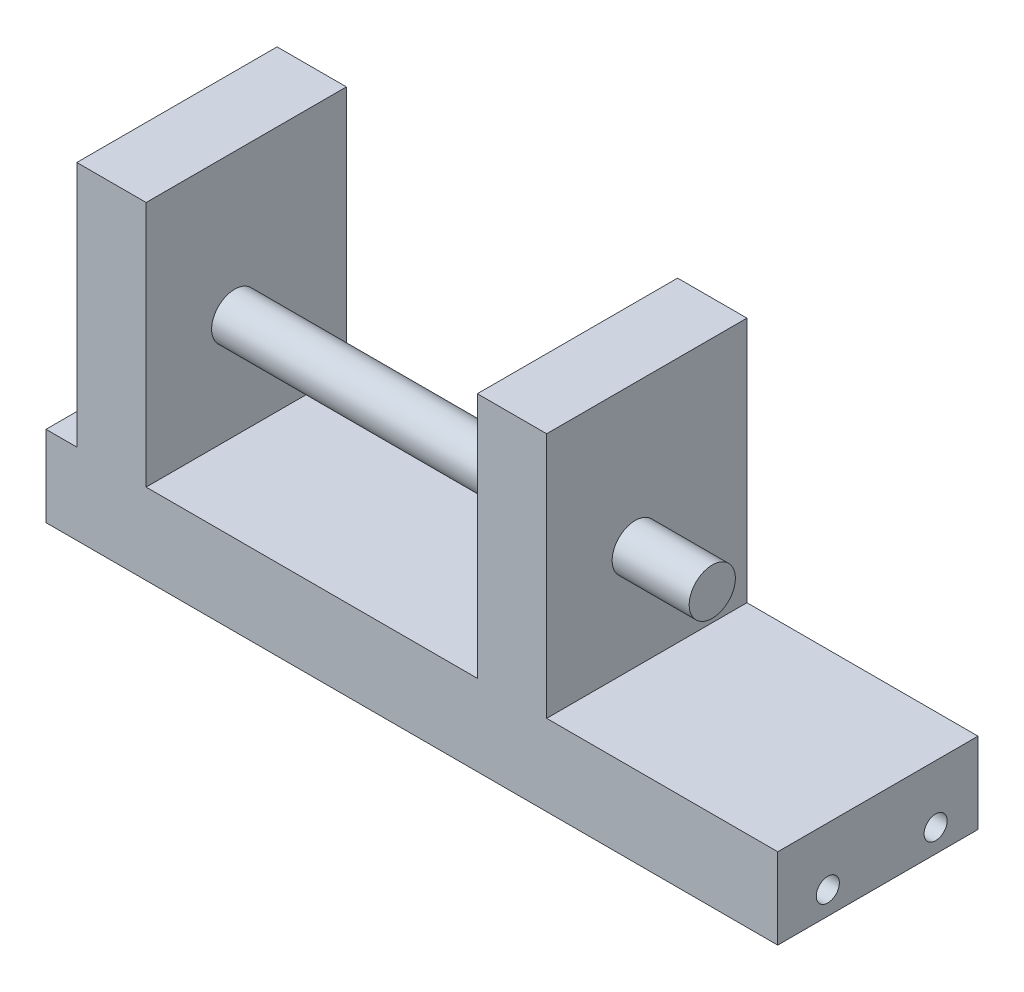
SolidWorks part; units mm, degrees
ref_plane "前视基准面" through (0, 0, 0) normal (0, 0, 1) x (1, 0, 0)
ref_plane "上视基准面" through (0, 0, 0) normal (0, 1, 0) x (1, 0, 0)
ref_plane "右视基准面" through (0, 0, 0) normal (1, 0, 0) x (0, 0, -1)
sketch "草图1" plane through (0, 0, 0) normal (1, 0, 0) x (0, 0, -1)
  line L0 (-19.5, 10.5) -> (-19.5, 3) construction
  line L1 (-26, 10.5) -> (0, 10.5)
  line L2 (-26, 10.5) -> (-26, 0)
  line L3 (-26, 0) -> (0, 0)
  line L4 (0, 10.5) -> (0, 0)
  line L5 (-19.5, 3) -> (-26, 3) construction
  line L6 (-19.5, 3) -> (-5.5, 3) construction
  line L7 (-5.5, 3) -> (0, 3) construction
  line L8 (-19.5, 3) -> (-19.5, 24) construction
  line L9 (-19.5, 24) -> (-14.5, 24) construction
  line L10 (-14.5, 24) -> (-5.5, 24) construction
  line L11 (-5.5, 24) -> (-5.5, 3) construction
  circle A0 centre (-19.5, 3) radius 1.5
  circle A1 centre (-5.5, 3) radius 1.5
  circle A2 centre (-14.5, 24) radius 3 construction
  dimension "D5" = 3
  dimension "D7" = 3
  dimension "D11" = 6
  dimension "D1" = 26
  dimension "D2" = 10.5
  dimension "D3" = 6.5
  dimension "D4" = 7.5
  dimension "D6" = 5.5
  dimension "D8" = 21
  dimension "D9" = 5
  dimension "D10" = 9
extrude "凸台-拉伸1" add sketch "草图1" against normal blind 95
sketch "草图2" plane through (0, 10.5, 0) normal (0, 1, 0) x (1, 0, 0)
  line L0 (0, -18.8173) -> (-30, -18.8173) construction
  line L1 (0, 0) -> (0, -26) construction
  line L2 (-95, -26) -> (0, -26) construction
  line L3 (-39, 0) -> (-30, 0)
  line L4 (-39, 0) -> (-39, -26)
  line L5 (-39, -26) -> (-30, -26)
  line L6 (-30, 0) -> (-30, -26)
  line L7 (-95, 0) -> (0, 0) construction
  line L8 (-30, -18.8173) -> (-91, -18.8173) construction
  line L9 (-91, 0) -> (-82, 0)
  line L10 (-91, 0) -> (-91, -26)
  line L11 (-91, -26) -> (-82, -26)
  line L12 (-82, 0) -> (-82, -26)
  dimension "D1" = 30
  dimension "D2" = 61
  dimension "D3" = 9
extrude "凸台-拉伸2" add sketch "草图2" along normal blind 32
sketch "草图4" plane through (-30, 0, 0) normal (1, 0, 0) x (0, 0, -1)
  line L0 (-26, 10.5) -> (-14.5, 10.5) construction
  line L1 (-26, 10.5) -> (0, 10.5) construction
  line L2 (-14.5, 10.5) -> (-14.5, 24) construction
  circle A0 centre (-14.5, 24) radius 3
  dimension "D3" = 6
  dimension "D1" = 13.5
  dimension "D2" = 11.5
extrude "凸台-拉伸3" add sketch "草图4" along direction (-1, 0, 0) on the side against the normal up to surface (52 mm away) contours A0 up to face at (-82, 26.5, 13)
extrude "凸台-拉伸4" add sketch "草图4<5>" along normal blind 10
sketch "草图4<5>" plane through (-30, 0, 0) normal (1, 0, 0) x (0, 0, -1) same geometry as "草图4"
